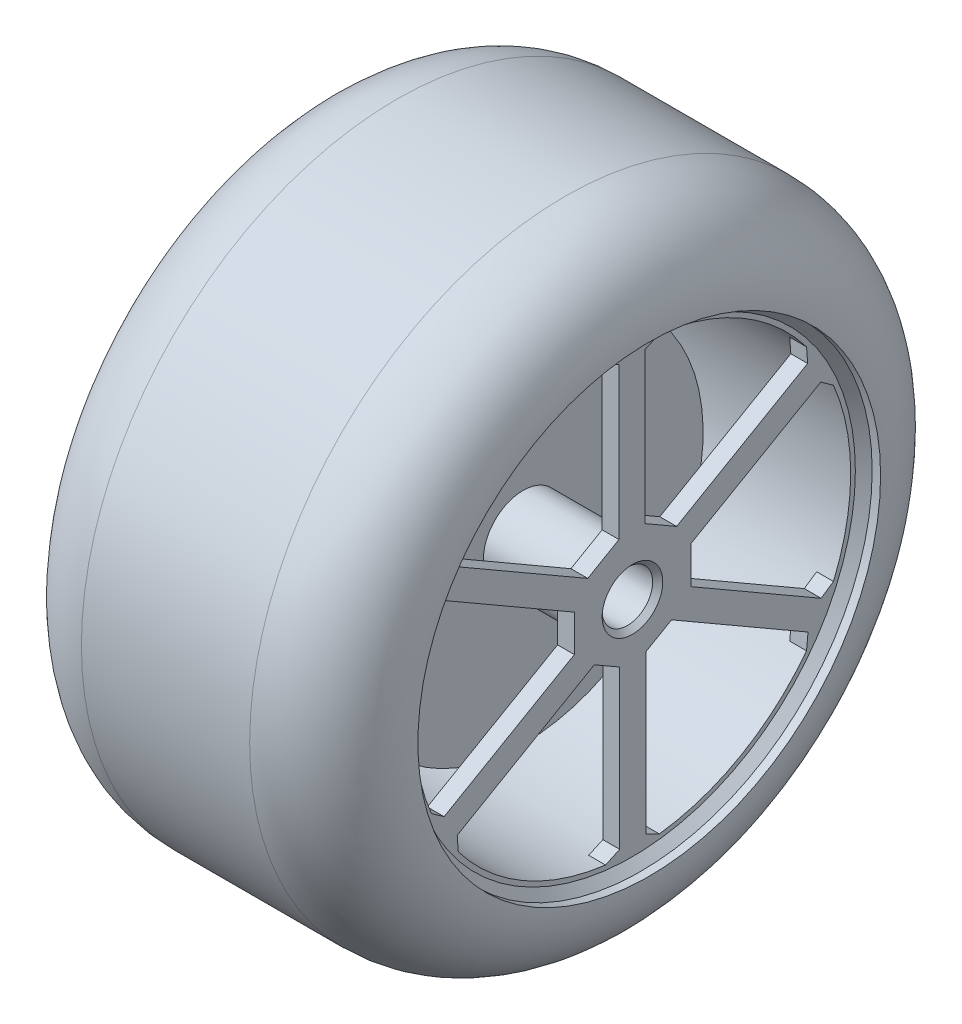
SolidWorks part; units mm, degrees
ref_plane "Front Plane" through (0, 0, 0) normal (0, 0, 1) x (1, 0, 0)
ref_plane "Top Plane" through (0, 0, 0) normal (0, 1, 0) x (1, 0, 0)
ref_plane "Right Plane" through (0, 0, 0) normal (1, 0, 0) x (0, 0, -1)
sketch "Sketch1" plane through (0, 0, 0) normal (1, 0, 0) x (0, 0, -1)
  circle A0 centre (0, 0) radius 18.75
  circle A1 centre (0, 0) radius 13.75
  dimension "D1" = 37.5
  dimension "D2" = 27.5
extrude "Boss-Extrude1" add sketch "Sketch1" along normal blind 20
fillet "Fillet1" radius 5 2 edges at (0, 0, -18.75) (20, 0, -18.75)
ref_plane "Plane1" through (19, 0, 0) normal (1, 0, 0) x (0, 0, -1)
sketch "Sketch2" plane through (19, 0, 0) normal (1, 0, 0) x (0, 0, -1)
  circle A0 centre (0, 0) radius 13.75
  circle A1 centre (0, 0) radius 12.9719
extrude "Boss-Extrude2" add sketch "Sketch2" against normal blind 19
chamfer "Chamfer2" distance 0.5 angle 45 1 edges at (19, 0, -13.75)
sketch "Sketch3" plane through (19, 0, 0) normal (1, 0, 0) x (0, 0, -1)
  line L0 (-0.8, 12.4868) -> (-0.8, 2.564)
  line L1 (0.7575, 12.4868) -> (0.7575, 2.564)
  line L2 (-1.6, 12.8729) -> (-0.8, 12.4868)
  line L3 (0.7575, 12.4868) -> (1.6, 12.8729)
  line L4 (-0.8, 2.564) -> (0.7575, 2.564)
  arc A1 (-1.6, 12.8729) -> (1.6, 12.8729) centre (0, 3.9908) cw
  circle A2 centre (0, 0) radius 12.9719 construction
  dimension "D1" = 1.5575
  dimension "D2" = 0.8
  dimension "D3" = 1.6
  dimension "D4" = 1.6
extrude "Boss-Extrude3" add sketch "Sketch3" against normal blind 1
pattern_circular "CirPattern1" count 6 over 360 about axis through (19, 0, 0) along (1, 0, 0) of "Boss-Extrude3"
sketch "Sketch4" plane through (19, 0, 0) normal (1, 0, 0) x (0, 0, -1)
  line L0 (-3.45, 1.95) -> (0.0141, 3.95)
  line L2 (0.0141, 3.95) -> (3.4782, 1.95)
  line L3 (3.4782, 1.95) -> (3.4782, -1.55)
  line L4 (3.4782, -1.55) -> (0.0141, -3.55)
  line L5 (0.0141, -3.55) -> (-3.45, -1.55)
  line L6 (-3.45, -1.55) -> (-3.45, 1.95)
  dimension "D1" = 4
  dimension "D2" = 4
  dimension "D3" = 3.5
  dimension "D4" = 4
  dimension "D5" = 4
  dimension "D6" = 120
  dimension "D7" = 120
  dimension "D8" = 120
  dimension "D9" = 3.45
  dimension "D10" = 3.55
extrude "Boss-Extrude4" add sketch "Sketch4" against normal blind 1
ref_plane "Plane2" through (10, 0, 0) normal (1, 0, 0) x (0, 0, -1)
mirror "Mirror1" about plane through (10, 0, 0) normal (1, 0, 0) of "CirPattern1", "Boss-Extrude4"
ref_plane "Plane3" through (10, 0, 0) normal (1, 0, 0) x (0, 0, -1)
sketch "Sketch7" plane through (10, 0, 0) normal (1, 0, 0) x (0, 0, -1)
  circle A0 centre (0, 0) radius 10.7011
extrude "Boss-Extrude5" add sketch "Sketch7" along normal blind 2.5 separate body
sketch "Sketch8" plane through (12.5, 0, 0) normal (1, 0, 0) x (0, 0, -1)
  circle A0 centre (0, 0) radius 2.3574
extrude "Boss-Extrude6" add sketch "Sketch8" along normal blind 6
sketch "Sketch9" plane through (12.5, 0, 0) normal (1, 0, 0) x (0, 0, -1)
  spline S0 degree 3 poles (-6.3532, 9.7507) (-8.1123, 9.7292) (-10.9019, 2.5459) (-12.9547, -0.6784) (-9.5647, -3.8397) (-9.4244, 2.6265) (-2.1221, 8.945) (-3.9441, 9.735) (-6.3532, 9.7507) (-8.1123, 9.7292) (-10.9019, 2.5459) knots -0.246542 -0.176965 -0.019663 0 0.161931 0.192354 0.291797 0.354142 0.753458 0.823035 0.980337 1 1.161931 1.192354 1.291797 only from (-7.3908, 9.6663) to (-7.3908, 9.6663)
extrude "Boss-Extrude7" add sketch "Sketch9" along normal blind 2
mirror "Mirror4" about plane through (10, 0, 0) normal (1, 0, 0) of "Boss-Extrude6"
sketch "Sketch10" plane through (10, 0, 0) normal (-1, 0, 0) x (0, 0, 1)
  circle A0 centre (0, 0) radius 10.7011
extrude "Boss-Extrude8" add sketch "Sketch10" along normal blind 2.5
mirror "Mirror6" about plane through (10, 0, 0) normal (1, 0, 0) of "Boss-Extrude7"
sketch "Sketch11" plane through (19, 0, 0) normal (1, 0, 0) x (0, 0, -1)
  circle A0 centre (0, 0) radius 1.5
  dimension "D1" = 3
extrude "Cut-Extrude1" cut sketch "Sketch11" against normal blind 4
chamfer "Chamfer3" distance 0.1 angle 45 1 edges at (15, 0, -1.5)
chamfer "Chamfer4" distance 0.3 angle 45 1 edges at (19, 0, -1.5)
